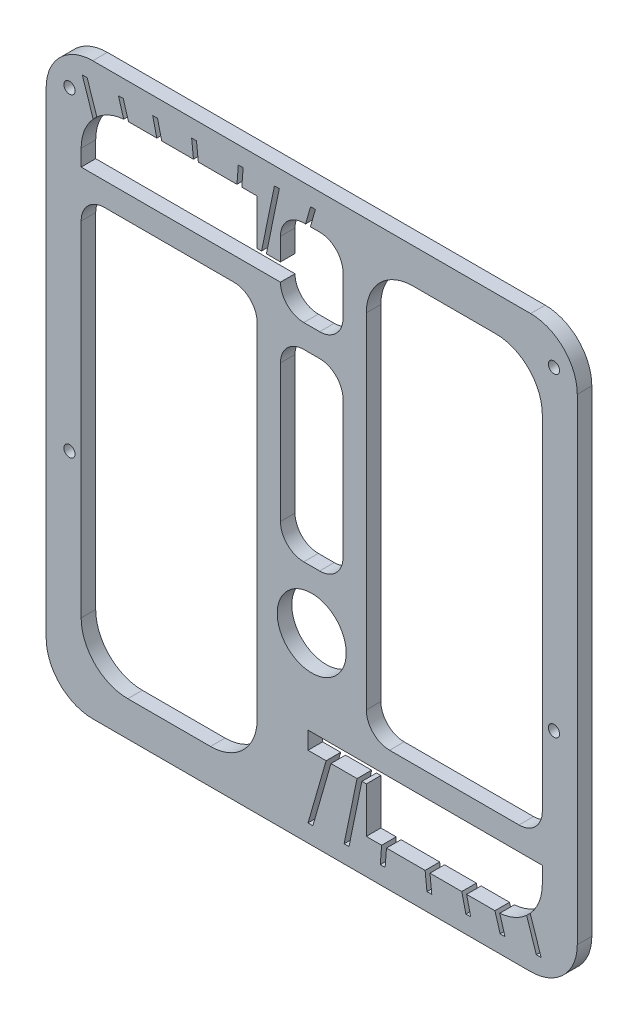
SolidWorks part; units mm, degrees
ref_plane "Front Plane" through (0, 0, 0) normal (0, 0, 1) x (1, 0, 0)
ref_plane "Top Plane" through (0, 0, 0) normal (0, 1, 0) x (1, 0, 0)
ref_plane "Right Plane" through (0, 0, 0) normal (1, 0, 0) x (0, 0, -1)
sketch "Sketch1" plane through (0, 0, 0) normal (0, 0, 1) x (1, 0, 0)
  line L0 (-9.8234, 48.7906) -> (-9.8234, 44.9806) construction
  line L1 (-16.441, -13.3096) -> (41.4264, -13.3096)
  line L2 (-16.441, -13.3096) -> (-16.441, 48.7906)
  line L3 (-16.441, 48.7906) -> (41.4264, 48.7906)
  line L4 (41.4264, -13.3096) -> (41.4264, 48.7906)
  line L6 (-9.8234, 46.8856) -> (-20.2694, 46.8856) construction
  line L7 (-11.9754, 46.8856) -> (-12.504, 46.8856) construction
  line L8 (36.4915, -9.4996) -> (36.4915, -13.3096) construction
  line L10 (-12.631, 44.9806) -> (37.6164, 44.9806)
  line L11 (-12.631, 44.9806) -> (-12.631, -9.4996)
  line L12 (-12.631, -9.4996) -> (37.6164, -9.4996)
  line L13 (37.6164, 44.9806) -> (37.6164, -9.4996)
  line L14 (36.4915, -11.4046) -> (50.994, -11.4046) construction
  line L15 (36.9608, -11.4046) -> (37.4894, -11.4046) construction
  line L16 (37.6164, 41.4945) -> (41.4264, 41.4945) construction
  line L17 (39.5214, 41.4945) -> (39.5214, -21.3698) construction
  line L18 (39.5214, 23.3666) -> (39.5214, 35.6094) construction
  line L19 (-12.631, 40.8837) -> (-16.441, 40.8837) construction
  line L20 (-14.536, 40.8837) -> (-14.536, -26.4843) construction
  line L21 (-14.536, 12.1144) -> (-14.536, -0.1284) construction
  dimension "D1" = 3.81
  dimension "D2" = 3.81
extrude "Boss-Extrude1" add sketch "Sketch1" along normal blind 1.5875
fillet "Fillet3" radius 5.08 4 edges at (37.6164, -9.4996, 0.7937) (-12.631, -9.4996, 0.7937) (37.6164, 44.9806, 0.7937) (-12.631, 44.9806, 0.7937)
sketch "Sketch6" plane through (0, 0, 1.5875) normal (0, 0, 1) x (1, 0, 0)
  line L0 (32.5364, 44.9806) -> (-7.551, 44.9806) construction
  line L1 (-12.631, 39.9006) -> (-12.631, -4.4196) construction
  line L2 (37.6164, -4.4196) -> (37.6164, 39.9006) construction
  line L3 (37.6164, 13.0034) -> (37.6164, 0.405)
  line L4 (18.4394, 44.9806) -> (6.546, 44.9806)
  line L5 (-12.631, 0.405) -> (-12.631, 13.0034)
  line L6 (18.4394, 44.9806) -> (18.4394, -9.4996)
  line L7 (18.4394, -9.4996) -> (6.546, -9.4996)
  line L9 (6.546, 44.9806) -> (6.546, -9.4996)
  line L10 (-7.551, -9.4996) -> (32.5364, -9.4996) construction
  line L11 (8.7335, 6.7042) -> (8.7335, 12.2237) construction
  line L12 (16.2519, 6.7042) -> (16.2519, 13.4807) construction
  line L13 (6.546, 31.0374) -> (6.546, -0.1284) construction
  line L14 (18.4394, 4.4436) -> (18.4394, 35.6094) construction
  circle A0 centre (12.4927, 6.7042) radius 3.7592 construction
  circle A1 centre (12.4927, 6.7042) radius 3.7592
extrude "Boss-Extrude2" add sketch "Sketch6" against normal up to surface (1.5875 mm away) contours L4 L9 L7 L6 A1 region at (12.4927, 18.5523, 1.5875) up to face at (12.4927, 17.7405, 0)
sketch "Sketch4" plane through (0, 0, 1.5875) normal (0, 0, 1) x (1, 0, 0)
  line L6 (18.4394, 35.6094) -> (18.4394, 4.4436) construction
  line L7 (18.4394, 4.4436) -> (37.4894, 4.4436) construction
  line L8 (37.4894, 4.4436) -> (37.4894, 35.6094) construction
  line L9 (-12.504, 40.0276) -> (-12.504, 38.1226) construction
  line L10 (-12.504, 38.1226) -> (12.896, 38.1226) construction
  line L11 (12.896, 38.1226) -> (12.896, 40.0276) construction
  line L12 (12.896, 40.0276) -> (10.9227, 40.0276) construction
  line L13 (10.9227, 40.0276) -> (12.896, 46.8856) construction
  line L14 (12.896, 46.8856) -> (12.3674, 46.8856) construction
  line L15 (12.3674, 46.8856) -> (10.3941, 40.0276) construction
  line L16 (10.3941, 40.0276) -> (7.5541, 40.0276) construction
  line L17 (7.5541, 40.0276) -> (8.959, 46.8856) construction
  line L18 (8.959, 46.8856) -> (8.4304, 46.8856) construction
  line L19 (8.4304, 46.8856) -> (7.0255, 40.0276) construction
  line L20 (7.0255, 40.0276) -> (4.4934, 40.0276) construction
  line L21 (4.4934, 40.0276) -> (5.022, 46.8856) construction
  line L22 (5.022, 46.8856) -> (4.4934, 46.8856) construction
  line L23 (4.4934, 46.8856) -> (3.9648, 40.0276) construction
  line L24 (3.9648, 40.0276) -> (0.658, 40.0276) construction
  line L25 (0.658, 40.0276) -> (-0.0628, 46.8856) construction
  line L26 (-0.0628, 46.8856) -> (-0.5914, 46.8856) construction
  line L27 (-0.5914, 46.8856) -> (0.1294, 40.0276) construction
  line L28 (0.1294, 40.0276) -> (-2.6948, 40.0276) construction
  line L29 (-2.6948, 40.0276) -> (-4.3046, 46.8856) construction
  line L30 (-4.3046, 46.8856) -> (-4.8332, 46.8856) construction
  line L31 (-4.8332, 46.8856) -> (-3.2234, 40.0276) construction
  line L32 (-3.2234, 40.0276) -> (-5.9968, 40.0276) construction
  line L33 (-5.9968, 40.0276) -> (-8.0384, 46.8856) construction
  line L34 (-8.0384, 46.8856) -> (-8.567, 46.8856) construction
  line L35 (-8.567, 46.8856) -> (-6.5254, 40.0276) construction
  line L36 (-6.5254, 40.0276) -> (-9.71, 40.0276) construction
  line L37 (-9.71, 40.0276) -> (-11.9754, 46.8856) construction
  line L38 (-11.9754, 46.8856) -> (-12.504, 46.8856) construction
  line L39 (-12.504, 46.8856) -> (-10.2386, 40.0276) construction
  line L40 (-10.2386, 40.0276) -> (-12.504, 40.0276) construction
  line L47 (18.4394, 35.6094) -> (18.4394, 4.4436)
  line L48 (18.4394, 4.4436) -> (37.4894, 4.4436)
  line L49 (37.4894, 4.4436) -> (37.4894, 35.6094)
  line L50 (-12.504, 40.0276) -> (-12.504, 38.1226)
  line L51 (-12.504, 38.1226) -> (12.896, 38.1226)
  line L52 (12.896, 38.1226) -> (12.896, 40.0276)
  line L53 (12.896, 40.0276) -> (10.9227, 40.0276)
  line L54 (10.9227, 40.0276) -> (12.896, 46.8856)
  line L55 (12.896, 46.8856) -> (12.3674, 46.8856)
  line L56 (12.3674, 46.8856) -> (10.3941, 40.0276)
  line L57 (10.3941, 40.0276) -> (7.5541, 40.0276)
  line L58 (7.5541, 40.0276) -> (8.959, 46.8856)
  line L59 (8.959, 46.8856) -> (8.4304, 46.8856)
  line L60 (8.4304, 46.8856) -> (7.0255, 40.0276)
  line L61 (7.0255, 40.0276) -> (4.4934, 40.0276)
  line L62 (4.4934, 40.0276) -> (5.022, 46.8856)
  line L63 (5.022, 46.8856) -> (4.4934, 46.8856)
  line L64 (4.4934, 46.8856) -> (3.9648, 40.0276)
  line L65 (3.9648, 40.0276) -> (0.658, 40.0276)
  line L66 (0.658, 40.0276) -> (-0.0628, 46.8856)
  line L67 (-0.0628, 46.8856) -> (-0.5914, 46.8856)
  line L68 (-0.5914, 46.8856) -> (0.1294, 40.0276)
  line L69 (0.1294, 40.0276) -> (-2.6948, 40.0276)
  line L70 (-2.6948, 40.0276) -> (-4.3046, 46.8856)
  line L71 (-4.3046, 46.8856) -> (-4.8332, 46.8856)
  line L72 (-4.8332, 46.8856) -> (-3.2234, 40.0276)
  line L73 (-3.2234, 40.0276) -> (-5.9968, 40.0276)
  line L74 (-5.9968, 40.0276) -> (-8.0384, 46.8856)
  line L75 (-8.0384, 46.8856) -> (-8.567, 46.8856)
  line L76 (-8.567, 46.8856) -> (-6.5254, 40.0276)
  line L77 (-6.5254, 40.0276) -> (-9.71, 40.0276)
  line L78 (-9.71, 40.0276) -> (-11.9754, 46.8856)
  line L79 (-11.9754, 46.8856) -> (-12.504, 46.8856)
  line L80 (-12.504, 46.8856) -> (-10.2386, 40.0276)
  line L81 (-10.2386, 40.0276) -> (-12.504, 40.0276)
  line L88 (-14.5106, -1.1684) -> (37.4894, -1.1684)
  line L89 (37.4894, -1.1684) -> (37.4894, -0.1284)
  line L90 (37.4894, -0.1284) -> (6.546, -0.1284)
  line L91 (6.546, -0.1284) -> (-12.504, -0.1284)
  line L92 (-12.504, -0.1284) -> (-14.5106, -0.1284)
  line L93 (-14.5106, -0.1284) -> (-14.5106, -1.1684)
  line L95 (37.4894, -1.1684) -> (37.4894, -0.1284)
  line L114 (37.4894, -4.5466) -> (37.4894, -2.6416)
  line L115 (37.4894, -2.6416) -> (12.0894, -2.6416)
  line L116 (12.0894, -2.6416) -> (12.0894, -4.5466)
  line L117 (12.0894, -4.5466) -> (14.0627, -4.5466)
  line L118 (14.0627, -4.5466) -> (12.0894, -11.4046)
  line L119 (12.0894, -11.4046) -> (12.618, -11.4046)
  line L120 (12.618, -11.4046) -> (14.5913, -4.5466)
  line L121 (14.5913, -4.5466) -> (17.4313, -4.5466)
  line L122 (17.4313, -4.5466) -> (16.0264, -11.4046)
  line L123 (16.0264, -11.4046) -> (16.555, -11.4046)
  line L124 (16.555, -11.4046) -> (17.9599, -4.5466)
  line L125 (17.9599, -4.5466) -> (20.492, -4.5466)
  line L126 (20.492, -4.5466) -> (19.9634, -11.4046)
  line L127 (19.9634, -11.4046) -> (20.492, -11.4046)
  line L128 (20.492, -11.4046) -> (21.0206, -4.5466)
  line L129 (21.0206, -4.5466) -> (24.3274, -4.5466)
  line L130 (24.3274, -4.5466) -> (25.0482, -11.4046)
  line L131 (25.0482, -11.4046) -> (25.5768, -11.4046)
  line L132 (25.5768, -11.4046) -> (24.856, -4.5466)
  line L133 (24.856, -4.5466) -> (27.6802, -4.5466)
  line L134 (27.6802, -4.5466) -> (29.29, -11.4046)
  line L135 (29.29, -11.4046) -> (29.8186, -11.4046)
  line L136 (29.8186, -11.4046) -> (28.2088, -4.5466)
  line L137 (28.2088, -4.5466) -> (30.9822, -4.5466)
  line L138 (30.9822, -4.5466) -> (33.0238, -11.4046)
  line L139 (33.0238, -11.4046) -> (33.5524, -11.4046)
  line L140 (33.5524, -11.4046) -> (31.5108, -4.5466)
  line L141 (31.5108, -4.5466) -> (34.6954, -4.5466)
  line L142 (34.6954, -4.5466) -> (36.9608, -11.4046)
  line L143 (36.9608, -11.4046) -> (37.4894, -11.4046)
  line L144 (37.4894, -11.4046) -> (35.224, -4.5466)
  line L145 (35.224, -4.5466) -> (37.4894, -4.5466)
  line L146 (37.4894, -4.5466) -> (37.4894, -2.6416)
  line L147 (37.4894, -2.6416) -> (12.0894, -2.6416)
  line L148 (12.0894, -2.6416) -> (12.0894, -4.5466)
  line L149 (12.0894, -4.5466) -> (14.0627, -4.5466)
  line L150 (14.0627, -4.5466) -> (12.0894, -11.4046)
  line L151 (12.0894, -11.4046) -> (12.618, -11.4046)
  line L152 (12.618, -11.4046) -> (14.5913, -4.5466)
  line L153 (14.5913, -4.5466) -> (17.4313, -4.5466)
  line L154 (17.4313, -4.5466) -> (16.0264, -11.4046)
  line L155 (16.0264, -11.4046) -> (16.555, -11.4046)
  line L156 (16.555, -11.4046) -> (17.9599, -4.5466)
  line L157 (17.9599, -4.5466) -> (20.492, -4.5466)
  line L158 (20.492, -4.5466) -> (19.9634, -11.4046)
  line L159 (19.9634, -11.4046) -> (20.492, -11.4046)
  line L160 (20.492, -11.4046) -> (21.0206, -4.5466)
  line L161 (21.0206, -4.5466) -> (24.3274, -4.5466)
  line L162 (24.3274, -4.5466) -> (25.0482, -11.4046)
  line L163 (25.0482, -11.4046) -> (25.5768, -11.4046)
  line L164 (25.5768, -11.4046) -> (24.856, -4.5466)
  line L165 (24.856, -4.5466) -> (27.6802, -4.5466)
  line L166 (27.6802, -4.5466) -> (29.29, -11.4046)
  line L167 (29.29, -11.4046) -> (29.8186, -11.4046)
  line L168 (29.8186, -11.4046) -> (28.2088, -4.5466)
  line L169 (28.2088, -4.5466) -> (30.9822, -4.5466)
  line L170 (30.9822, -4.5466) -> (33.0238, -11.4046)
  line L171 (33.0238, -11.4046) -> (33.5524, -11.4046)
  line L172 (33.5524, -11.4046) -> (31.5108, -4.5466)
  line L173 (31.5108, -4.5466) -> (34.6954, -4.5466)
  line L174 (34.6954, -4.5466) -> (36.9608, -11.4046)
  line L175 (36.9608, -11.4046) -> (37.4894, -11.4046)
  line L176 (37.4894, -11.4046) -> (35.224, -4.5466)
  line L177 (35.224, -4.5466) -> (37.4894, -4.5466)
  line M210 (6.546, 44.9806) -> (6.546, -9.4996)
  line M212 (18.4394, -9.4996) -> (18.4394, 44.9806)
  line M224 (-7.551, 44.9806) -> (6.546, 44.9806)
  dimension "D1" = 0
  dimension "D2" = 0
extrude "Cut-Extrude4" cut sketch "Sketch4" against normal blind 2.54 contours L156 L157 L147 L148 L149 L150 L151 L152 L153 L154 L155 M212 | L159 L160 L158 | L163 L164 L162 | L167 L168 L166 | L171 L172 L170 | L175 L176 L174 | L67 L68 L66 | L63 L64 L62 | L59 L60 L51 L52 L53 L54 L55 L56 L57 L58 M210 | L75 L76 L74 | L79 L80 L78 | L71 L72 L70 M224 region at (-11.3713, 39.8179, 1.5875) region at (28.1464, -5.0536, 1.5875) region at (18.3312, -3.5941, 1.5875) region at (6.6542, 39.0751, 1.5875) region at (4.6843, 45.9331, 1.5875) region at (-0.227, 45.9331, 1.5875) region at (-4.3453, 45.9331, 1.5875)
sketch "Sketch7" plane through (0, 0, 1.5875) normal (0, 0, 1) x (1, 0, 0)
  line L0 (-12.631, 39.9006) -> (-12.631, -4.4196) construction
  line L1 (-12.631, 38.1226) -> (6.546, 38.1226)
  line L2 (-12.631, 38.1226) -> (-12.631, 35.5826)
  line L3 (-12.631, 35.5826) -> (6.546, 35.5826)
  line L4 (6.546, 38.1226) -> (6.546, 35.5826)
  line L5 (6.546, 38.1226) -> (6.546, -9.4996) construction
  line L9 (37.6164, -4.4196) -> (37.6164, 39.9006) construction
  line L10 (37.6164, -2.6416) -> (18.4394, -2.6416)
  line L11 (37.6164, -2.6416) -> (37.6164, -0.1016)
  line L12 (37.6164, -0.1016) -> (18.4394, -0.1016)
  line L13 (18.4394, -2.6416) -> (18.4394, -0.1016)
  line L14 (18.4394, 44.9806) -> (18.4394, -2.6416) construction
  line L16 (37.4894, -2.6416) -> (12.0894, -2.6416) construction
  line L19 (-12.504, 38.1226) -> (12.896, 38.1226) construction
  dimension "D1" = 2.54
  dimension "D2" = 2.54
extrude "Boss-Extrude3" add sketch "Sketch7" against normal up to surface (1.5875 mm away) up to face at (0.4837, 40.011, 0)
fillet "Fillet1" radius 5.08 4 edges at (-16.441, -13.3096, 0.7937) (41.4264, -13.3096, 0.7937) (41.4264, 48.7906, 0.7937) (-16.441, 48.7906, 0.7937)
fillet "Fillet4" radius 5.08 2 edges at (6.546, -9.4996, 0.7937) (18.4394, 44.9806, 0.7937)
sketch "Sketch8" plane through (0, 0, 1.5875) normal (0, 0, 1) x (1, 0, 0)
  line L0 (6.546, 35.5826) -> (6.546, -4.4196) construction
  line L1 (9.086, 44.9806) -> (15.8994, 44.9806)
  line L2 (9.086, 44.9806) -> (9.086, 13.0034)
  line L3 (9.086, 13.0034) -> (15.8994, 13.0034)
  line L4 (15.8994, 44.9806) -> (15.8994, 13.0034)
  line L5 (18.4394, 39.9006) -> (18.4394, -0.1016) construction
  line L7 (12.4927, 10.4634) -> (-0.3555, 10.4634) construction
  line L8 (12.4927, 6.7042) -> (12.4927, 10.4634) construction
  line L9 (6.546, 44.9806) -> (4.8752, 44.9806) construction
  line L10 (9.086, 35.5826) -> (15.8994, 35.5826)
  line L11 (-12.631, 35.5826) -> (6.546, 35.5826) construction
  line L12 (9.086, 33.0426) -> (15.8994, 33.0426)
  circle A1 centre (12.4927, 6.7042) radius 3.7592 construction
  dimension "D1" = 2.54
  dimension "D2" = 2.54
  dimension "D3" = 2.54
  dimension "D4" = 2.54
extrude "Cut-Extrude5" cut sketch "Sketch8" against normal up to surface (1.5875 mm away) contours L2 L10 L4 L1 | L12 L2 L3 L4 region at (12.4927, 40.2816, 1.5875) region at (12.4927, 23.023, 1.5875) up to face at (24.5911, -8.7801, 0)
fillet "Fillet5" radius 2.54 4 edges at (15.8994, 13.0034, 0.7937) (9.086, 13.0034, 0.7937) (15.8994, 44.9806, 0.7937) (9.086, 44.9806, 0.7937)
fillet "Fillet6" radius 2.54 4 edges at (6.546, 35.5826, 0.7937) (18.4394, -0.1016, 0.7937) (37.6164, -0.1016, 0.7937) (-12.631, 35.5826, 0.7937)
fillet "Fillet7" radius 2.54 4 edges at (15.8994, 35.5826, 0.7937) (15.8994, 33.0426, 0.7937) (9.086, 33.0426, 0.7937) (9.086, 35.5826, 0.7937)
sketch "Sketch9" plane through (0, 0, 1.5875) normal (0, 0, 1) x (1, 0, 0)
  line L1 (-16.441, 43.7106) -> (-16.441, -8.2296) construction
  line L2 (-11.361, -13.3096) -> (36.3464, -13.3096) construction
  line L6 (36.3464, 48.7906) -> (-11.361, 48.7906) construction
  line L7 (41.4264, -8.2296) -> (41.4264, 43.7106) construction
  circle A0 centre (-13.901, 44.9806) radius 0.6096
  circle A1 centre (38.8864, 44.9806) radius 0.6096
  circle A2 centre (38.8864, 10.6934) radius 0.6096
  circle A3 centre (-13.901, 10.6934) radius 0.6096
  dimension "D1" = 1.2192
  dimension "D2" = 3.81
  dimension "D3" = 2.54
  dimension "D4" = 2.54
  dimension "D5" = 24.003
extrude "Cut-Extrude6" cut sketch "Sketch9" against normal up to surface (1.5875 mm away) up to face at (12.4927, 23.023, 0)
